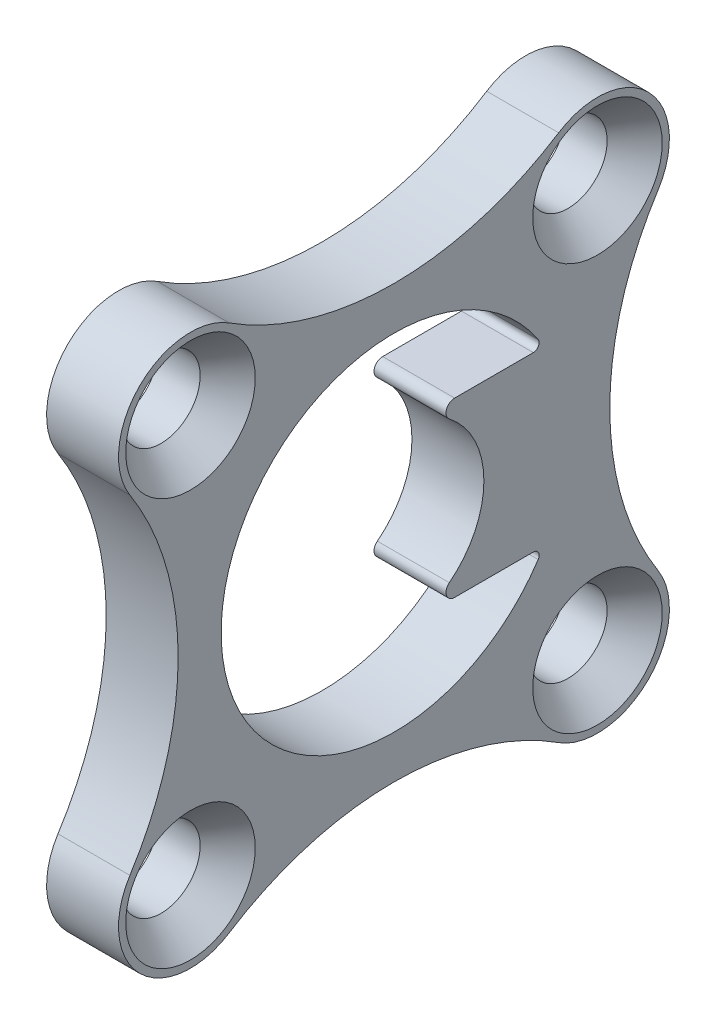
SolidWorks part; units mm, degrees
material "6061-T6 (SS)"
ref_plane "Front Plane" through (0, 0, 0) normal (0, 0, 1) x (1, 0, 0)
ref_plane "Top Plane" through (0, 0, 0) normal (0, 1, 0) x (1, 0, 0)
ref_plane "Right Plane" through (0, 0, 0) normal (1, 0, 0) x (0, 0, -1)
sketch "Sketch1" plane through (-42.95, 0, 0) normal (-1, 0, 0) x (0, 0, 1)
  line L0 (-6.1518, 3.81) -> (-2.6762, 3.81)
  line L1 (-7.8431, 3.81) -> (-5.999, 3.81) construction
  line L2 (-2.6762, -3.81) -> (-6.1518, -3.81)
  line L3 (-7.8431, -3.81) -> (-2.8575, -3.81) construction
  line L5 (-5.999, 3.81) -> (-1.1112, 3.81) construction
  line L6 (8.9803, 8.9803) -> (-8.9803, -8.9803) construction
  line L7 (8.9803, -8.9803) -> (-8.9803, 8.9803) construction
  arc A0 (-2.6762, 3.81) -> (-2.4418, 3.1286) centre (-2.6762, 3.429) cw
  arc A1 (-2.4418, 3.1286) -> (-2.4418, -3.1286) centre (0, 0) ccw
  arc A2 (-2.4418, -3.1286) -> (-2.6762, -3.81) centre (-2.6762, -3.429) cw
  circle A3 centre (0, 0) radius 3.9687 construction
  circle A4 centre (0, 0) radius 3.9687 construction
  arc A5 (-6.1518, 3.81) -> (-6.3638, 4.204) centre (-6.1518, 4.064) cw
  arc A8 (-6.3638, 4.204) -> (-6.3638, -4.204) centre (0, 0) cw
  arc A9 (-6.3638, -4.204) -> (-6.1518, -3.81) centre (-6.1518, -4.064) cw
  circle A10 centre (0, 0) radius 15.875
  arc A11 (-6.2093, -4.2065) -> (-6.2093, 4.2065) centre (0, 0) ccw construction
  circle A12 centre (-8.9803, 8.9803) radius 3.175 construction
  circle A13 centre (-8.9803, 8.9803) radius 2.6924 construction
  circle A14 centre (0, 0) radius 9.525 construction
  dimension "D1" = 0.381
  dimension "D2" = 0.254
  dimension "D3" = 25.4
  dimension "D4" = 0.127
  dimension "D6" = 5.3848
  dimension "D7" = 19.05
  dimension "D5" = 45
extrude "Boss-Extrude1" add sketch "Sketch1" against normal blind 3.175
sketch "Sketch2" plane through (-42.95, 0, 0) normal (-1, 0, 0) x (0, 0, 1)
  line L0 (8.9803, -8.9803) -> (-8.9803, 8.9803) construction
  line L2 (0, 9.525) -> (0, 15.875)
  arc A0 (-11.2253, 11.2253) -> (0, 15.875) centre (0, 0) cw
  circle A1 centre (0, 0) radius 15.875 construction
  circle A3 centre (0, 0) radius 9.525 construction
  arc A5 (-7.2673, 11.6536) -> (-11.2253, 11.2253) centre (-8.9803, 8.9803) ccw
  circle A6 centre (-8.9803, 8.9803) radius 3.175 construction
  arc A7 (-7.2673, 11.6536) -> (0, 9.525) centre (0, 22.9954) ccw
  point P10 (0, 0)
extrude "Cut-Extrude1" cut sketch "Sketch2" against normal through all
mirror "Mirror1" about plane through (-39.775, 9.525, 0) normal (0, 0, 1) of "Cut-Extrude1"
pattern_circular "CirPattern2" count 4 over 360 about axis through (-42.95, 0, 0) along (-1, 0, 0) of "Cut-Extrude1", "Mirror1"
hole_wizard "CSK for #4 Flat Head Machine Screw1" positions "Sketch3" profile "Sketch4" countersink size "#4" standard "ANSI Inch" end condition up to next
sketch "Sketch3" plane through (-39.775, 0, 0) normal (1, 0, 0) x (0, 0, -1)
  point P0 (8.9803, -8.9803)
  point P3 (8.9803, -8.9803)
  point P6 (8.9803, -8.9803)
  point P9 (8.9803, -8.9803)
  point P13 (8.9803, 8.9803)
  point P16 (-8.9803, 8.9803)
  point P19 (-8.9803, -8.9803)
sketch "Sketch4" plane through (-39.775, -8.9803, -8.9803) normal (0, 1, 0) x (0, 0, -1)
  line L0 (0, 0) -> (0, 3.175)
  line L1 (0, 3.175) -> (1.7272, 3.175)
  line L2 (1.7272, 3.175) -> (1.7272, 1.3003)
  line L3 (1.7272, 1.3003) -> (2.8575, 0)
  line L5 (2.8575, 0) -> (0, 0)
  line L6 (-1.7272, 1.3003) -> (-2.8575, 0) construction
  line L11 (0, -6.35) -> (0, 107.95) construction
  dimension "Thru Hole Dia." = 3.4544
  dimension "Thru Hole Depth" = 3.175
  dimension "Near C'Sink Dia." = 5.715
  dimension "Near C'Sink Angle" = 82
